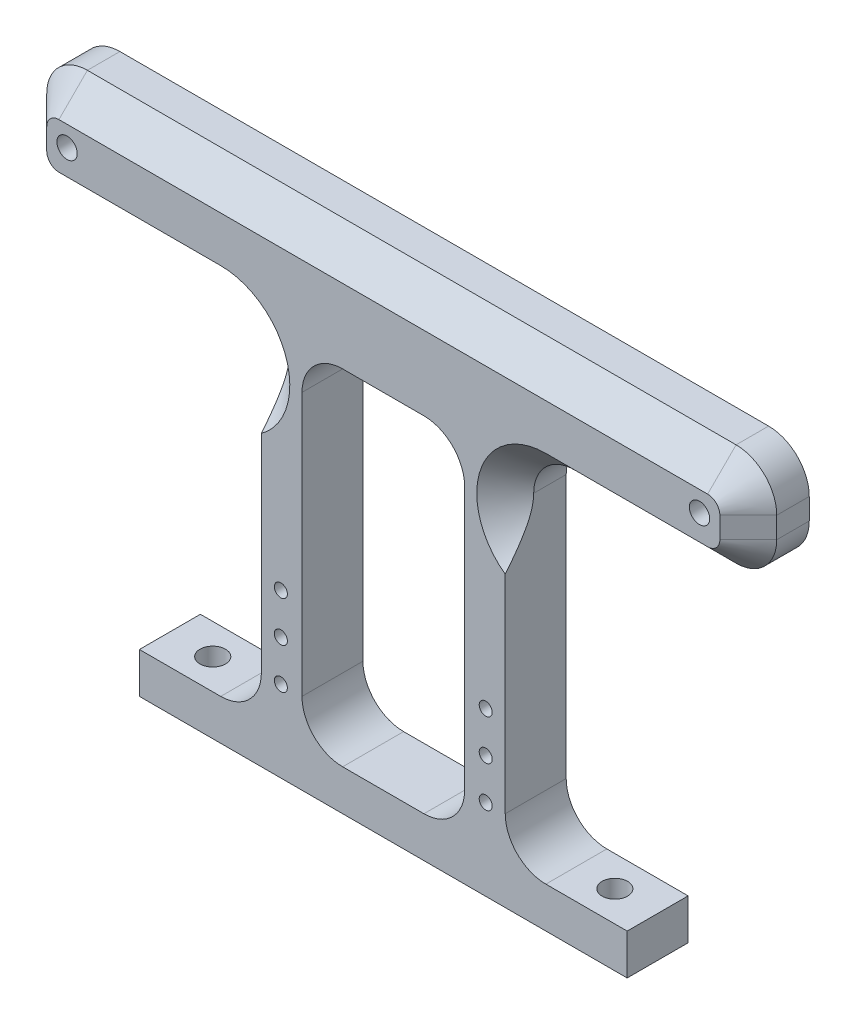
SolidWorks part; units mm, degrees
ref_plane "Front Plane" through (0, 0, 0) normal (0, 0, 1) x (1, 0, 0)
ref_plane "Top Plane" through (0, 0, 0) normal (0, 1, 0) x (1, 0, 0)
ref_plane "Right Plane" through (0, 0, 0) normal (1, 0, 0) x (0, 0, -1)
sketch "Sketch1" plane through (0, 0, 0) normal (0, 0, 1) x (1, 0, 0)
  line L0 (57.023, 60.1851) -> (57.023, 76.2)
  line L1 (-38.1, 0) -> (38.1, 0)
  line L2 (57.023, 76.2) -> (-57.023, 76.2)
  line L3 (-57.023, 76.2) -> (-57.023, 60.1851)
  line L4 (0, 0) -> (0, 101.7984) construction
  line L5 (-40.4874, 0) -> (40.4874, 0) construction
  line L6 (12.7, 60.1851) -> (12.7, 6.35)
  line L7 (-12.7, 6.35) -> (12.7, 6.35)
  line L8 (19.05, 6.35) -> (19.05, 60.1851)
  line L9 (19.05, 60.1851) -> (57.023, 60.1851)
  line L10 (-19.05, 60.1851) -> (-57.023, 60.1851)
  line L11 (-19.05, 6.35) -> (-19.05, 60.1851)
  line L12 (12.7, 60.1851) -> (-12.7, 60.1851)
  line L13 (-38.1, 0) -> (-38.1, 6.35)
  line L14 (-38.1, 6.35) -> (-19.05, 6.35)
  line L16 (38.1, 0) -> (38.1, 6.35)
  line L17 (38.1, 6.35) -> (19.05, 6.35)
  line L19 (-12.7, 60.1851) -> (-12.7, 6.35)
  circle A0 centre (-49.403, 68.58) radius 1.5875
  circle A1 centre (49.403, 68.58) radius 1.5875
  point P31 (-57.023, 76.2)
  dimension "D1" = 3.175
  dimension "D2" = 7.62
  dimension "D3" = 76.2
  dimension "D4" = 7.62
  dimension "D5" = 98.806
  dimension "D6" = 76.2
  dimension "D7" = 25.4
  dimension "D8" = 16.0149
  dimension "D9" = 38.1
  dimension "D10" = 6.35
  dimension "D14" = 53.8351
extrude "Extrude1" add sketch "Sketch1" against normal blind 9.525
fillet "Fillet1" radius 6.35 4 edges at (57.023, 60.1851, -4.7625) (-57.023, 60.1851, -4.7625) (-57.023, 76.2, -4.7625) (57.023, 76.2, -4.7625)
fillet "Fillet2" radius 6.35 8 edges at (-12.7, 60.1851, -4.7625) (12.7, 60.1851, -4.7625) (-12.7, 6.35, -4.7625) (19.05, 6.35, -4.7625) (-19.05, 6.35, -4.7625) (12.7, 6.35, -4.7625) (19.05, 60.1851, -4.7625) (-19.05, 60.1851, -4.7625)
chamfer "Chamfer3" distance 4.445 angle 45 7 edges at (38.0365, 60.1851, 0) (57.023, 68.1925, 0) (0, 76.2, 0) (-38.0365, 60.1851, 0) (-57.023, 68.1925, 0) (20.9099, 58.3252, 0) (-20.9099, 58.3252, 0)
sketch "Sketch2" plane through (0, 6.35, 0) normal (0, 1, 0) x (1, 0, 0)
  line L0 (31.411, 9.525) -> (31.411, 0) construction
  line L1 (50.673, 9.525) -> (-50.673, 9.525) construction
  line L2 (38.1, 0) -> (25.4, 0) construction
  circle A0 centre (31.411, 4.7625) radius 2
  dimension "D1" = 4
  dimension "D2" = 6.689
extrude "Cut-Extrude1" cut sketch "Sketch2" against normal through all
mirror "Mirror1" about plane through (0, 0, 0) normal (1, 0, 0) of "Cut-Extrude1"
sketch "Sketch3" plane through (0, 0, 0) normal (0, 0, 1) x (1, 0, 0)
  line L1 (38.1, 0) -> (16.002, 0) construction
  line L2 (38.1, 0) -> (38.1, 25.4) construction
  line L3 (38.1, 25.4) -> (16.002, 25.4) construction
  line L4 (16.002, 0) -> (16.002, 25.4) construction
  circle A0 centre (16.002, 25.4) radius 1.016
  dimension "D3" = 2.032
  dimension "D1" = 22.098
  dimension "D2" = 25.4
extrude "Cut-Extrude2" cut sketch "Sketch3" against normal through all
mirror "Mirror2" about plane through (0, 0, 0) normal (1, 0, 0) of "Cut-Extrude2"
pattern_linear "LPattern1" count 3 spacing 6.35 along (0, -1, 0) of "Cut-Extrude2", "Mirror2"
